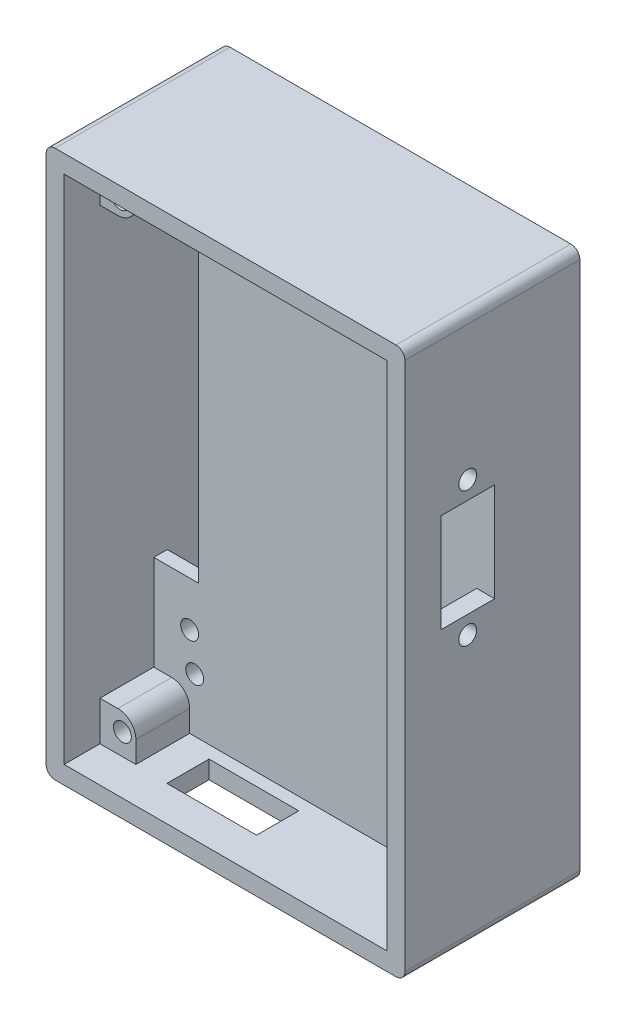
SolidWorks part; units mm, degrees
other "标注1"
sketch "草图16" plane through (38, 59, 11) normal (0.1952, 0.5523, 0.8105) x (0.9731, -0.0061, -0.2302)
other "标注2"
sketch "草图17" plane through (38, 59, 11) normal (0.1952, 0.5523, 0.8105) x (0.9731, -0.0061, -0.2302)
ref_plane "前视基准面" through (0, 0, 0) normal (0, 0, 1) x (1, 0, 0)
ref_plane "上视基准面" through (0, 0, 0) normal (0, 1, 0) x (1, 0, 0)
ref_plane "右视基准面" through (0, 0, 0) normal (1, 0, 0) x (0, 0, -1)
other "Configuration Table"
sketch "草图1" plane through (0, 0, 0) normal (0, 0, 1) x (1, 0, 0)
  line L1 (0, 0) -> (36, 0)
  line L2 (0, 0) -> (0, 57)
  line L3 (0, 57) -> (36, 57)
  line L4 (36, 0) -> (36, 57)
  line L5 (0, 15) -> (5, 15)
  line L6 (0, 15) -> (0, 51)
  line L7 (0, 51) -> (5, 51)
  line L8 (5, 15) -> (5, 51)
  line L9 (-2, 59) -> (-2, -2) construction
  line L10 (28.75, 16) -> (30.25, 16)
  line L11 (38, -2) -> (-2, -2) construction
  line L12 (28.75, 16) -> (28.75, 52)
  line L13 (38, -2) -> (38, 59) construction
  line L15 (38, 59) -> (-2, 59) construction
  line L16 (30.25, 16) -> (30.25, 52)
  line L17 (-1, -2) -> (37, -2)
  line L18 (-2, -1) -> (-2, 58)
  line L19 (-1, 59) -> (37, 59)
  line L20 (38, -1) -> (38, 58)
  line L21 (7.25, 52) -> (28.75, 52)
  line L23 (5.75, 53.5) -> (30.25, 53.5)
  line L24 (30.25, 52) -> (30.25, 53.5)
  line L25 (5.75, 46) -> (7.25, 46)
  line L26 (5.75, 46) -> (5.75, 53.5)
  line L28 (7.25, 46) -> (7.25, 52)
  line L29 (5.75, 16) -> (7.25, 16)
  line L30 (5.75, 16) -> (5.75, 25)
  line L31 (5.75, 25) -> (7.25, 25)
  line L32 (7.25, 16) -> (7.25, 25)
  circle A2 centre (4.56, 6) radius 1
  circle A3 centre (30.56, 6) radius 1
  circle A4 centre (4, 10) radius 1
  circle A5 centre (31, 10) radius 1
  arc A6 (37, -2) -> (38, -1) centre (37, -1) ccw
  arc A7 (-1, -2) -> (-2, -1) centre (-1, -1) cw
  arc A8 (38, 58) -> (37, 59) centre (37, 58) ccw
  arc A9 (-2, 58) -> (-1, 59) centre (-1, 58) cw
  point P20 (-2, -2)
  point P27 (38, -2)
  point P30 (-2, -2)
  point P33 (38, 59)
  dimension "D7" = 4
  dimension "D11" = 1
  dimension "D1" = 36
  dimension "D2" = 57
  dimension "D3" = 2
  dimension "D4" = 2
  dimension "D5" = 2
  dimension "D6" = 2
  dimension "D8" = 5
  dimension "D9" = 4.56
  dimension "D10" = 5.44
  dimension "D12" = 36
  dimension "D13" = 5
  dimension "D14" = 37.5
  dimension "D15" = 1.5
  dimension "D16" = 24.5
  dimension "D17" = 6
  dimension "D19" = 1.5
  dimension "D20" = 21.5
  dimension "D21" = 9
  dimension "D22" = 1.5
  dimension "D23" = 16
sketch "草图2" plane through (0, 0, 0) normal (0, 0, 1) x (1, 0, 0)
  line L7 (0, 0) -> (4, 0)
  line L8 (0, 0) -> (0, 4.4)
  line L9 (0, 4.4) -> (2, 4.4)
  line L10 (0, 0) -> (36, 0) construction
  line L13 (4, 0) -> (4, 2.4)
  line L14 (36, 0) -> (32, 0)
  line L15 (36, 0) -> (36, 4.4)
  line L16 (36, 4.4) -> (34, 4.4)
  line L17 (32, 0) -> (32, 2.4)
  line L18 (36, 57) -> (32, 57)
  line L19 (36, 57) -> (36, 52)
  line L20 (36, 52) -> (34, 52)
  line L21 (32, 57) -> (32, 54)
  line L22 (0, 57) -> (4, 57)
  line L23 (0, 57) -> (0, 52)
  line L24 (0, 52) -> (2, 52)
  line L25 (4, 57) -> (4, 54)
  circle A0 centre (2.5, 2.4) radius 1
  circle A1 centre (34, 2.4) radius 1
  circle A2 centre (2.25, 53.6994) radius 1
  circle A3 centre (33.75, 53.6994) radius 1
  arc A9 (4, 2.4) -> (2, 4.4) centre (2, 2.4) ccw
  arc A10 (34, 4.4) -> (32, 2.4) centre (34, 2.4) ccw
  arc A11 (34, 52) -> (32, 54) centre (34, 54) cw
  arc A12 (2, 52) -> (4, 54) centre (2, 54) ccw
  point P16 (2.0001, 0)
  point P18 (2, 4.3)
  point P25 (3.9, 2.4)
  point P28 (1.9999, 4.2999)
  dimension "D1" = 2
  dimension "D10" = 2
  dimension "D11" = 2
  dimension "D12" = 2
  dimension "D13" = 2
  dimension "D14" = 2
  dimension "D15" = 2
  dimension "D3" = 2.4
  dimension "D4" = 2.4
  dimension "D5" = 31.5
  dimension "D6" = 51.3
  dimension "D7" = 31.5
  dimension "D16" = 4
  dimension "D17" = 5
  dimension "D18" = 5
  dimension "D19" = 4
  dimension "D20" = 4
  dimension "D21" = 4.4
  dimension "D22" = 4.4
  dimension "D23" = 4
  dimension "D24" = 51.3
extrude "螺丝柱" add sketch "草图2" along normal blind 7.5
sketch "ESP32开口" plane through (0, 0, 0) normal (0, 1, 0) x (1, 0, 0)
  line L1 (12.56, 0) -> (22.56, 0)
  line L2 (12.56, 0) -> (12.56, 4.7)
  line L3 (12.56, 4.7) -> (22.56, 4.7)
  line L4 (22.56, 0) -> (22.56, 4.7)
  line L5 (38, 0) -> (-2, 0) construction
  dimension "D1" = 4.7
  dimension "D2" = 10
  dimension "D3" = 0
sketch "草图15" plane through (0, 0, 0) normal (0, -1, 0) x (1, 0, 0)
  line L1 (7.56, 2.9) -> (17.56, 2.9)
  line L2 (7.56, 2.9) -> (7.56, 7.6)
  line L3 (7.56, 7.6) -> (17.56, 7.6)
  line L4 (17.56, 2.9) -> (17.56, 7.6)
extrude "反向螺柱" add sketch "草图2<5>" against normal blind 4.5
sketch "草图2<5>" plane through (0, 0, 0) normal (0, 0, 1) x (1, 0, 0) same geometry as "草图2"
extrude "电源管理板外壳" add sketch "草图1" along normal blind 11.5 contours L17 L20 L19 L18 L4 L1 L2 L3 region at (-1.1913, -1.1913, 0)
extrude "电源管理板开口" cut sketch "草图15" along normal up to surface (2 mm away) up to face at (18, -2, 5.75)
extrude "ESP32外壳" add sketch "草图1" against normal blind 8 contours L17 L20 L19 L18 L4 L1 L2 L3 region at (-1.1913, -1.1913, 0)
extrude "ESP32" cut sketch "ESP32开口" against normal up to surface (2 mm away) up to face at (18, -2, 1.75)
extrude "底板" add sketch "草图1<29>" along normal blind 1.5 contours L8 L5 L2 L1 L4 L3 L7 A5 A4 A3 A2 L32 L29 L30 L31 L28 L25 L26 L23 L24 L16 L10 L12 L21 region at (19.3937, 27.4594, 0)
sketch "草图1<29>" plane through (0, 0, 0) normal (0, 0, 1) x (1, 0, 0) same geometry as "草图1"
extrude "凸台-拉伸3" add sketch "草图1<30>" against normal blind 2.5 separate body contours L25 L28 L21 L12 L10 L16 L24 L23 L26 | L29 L32 L31 L30 region at (29.1979, 34, 0) region at (6.5, 20.5, 0)
sketch "草图1<30>" plane through (0, 0, 0) normal (0, 0, 1) x (1, 0, 0) same geometry as "草图1"
extrude "凸台-拉伸4" add sketch "草图1<31>" along normal blind 1.5 contours L30 L31 L32 L29 | L12 L21 L28 L25 L26 L23 L24 L16 L10
sketch "草图1<31>" plane through (0, 0, 0) normal (0, 0, 1) x (1, 0, 0) same geometry as "草图1"
sketch "草图18" plane through (38, 0, 0) normal (1, 0, 0) x (0, 0, -1)
  line L1 (-7.5, 30) -> (-1.5, 30)
  line L2 (-7.5, 30) -> (-7.5, 41)
  line L3 (-7.5, 41) -> (-1.5, 41)
  line L4 (-1.5, 30) -> (-1.5, 41)
  circle A0 centre (-4.5, 43) radius 1
  circle A1 centre (-4.5, 28) radius 1
  dimension "D1" = 11
  dimension "D2" = 6
extrude "开关" cut sketch "草图18" against normal up to surface (2 mm away) up to face at (36, 28.35, 7)
